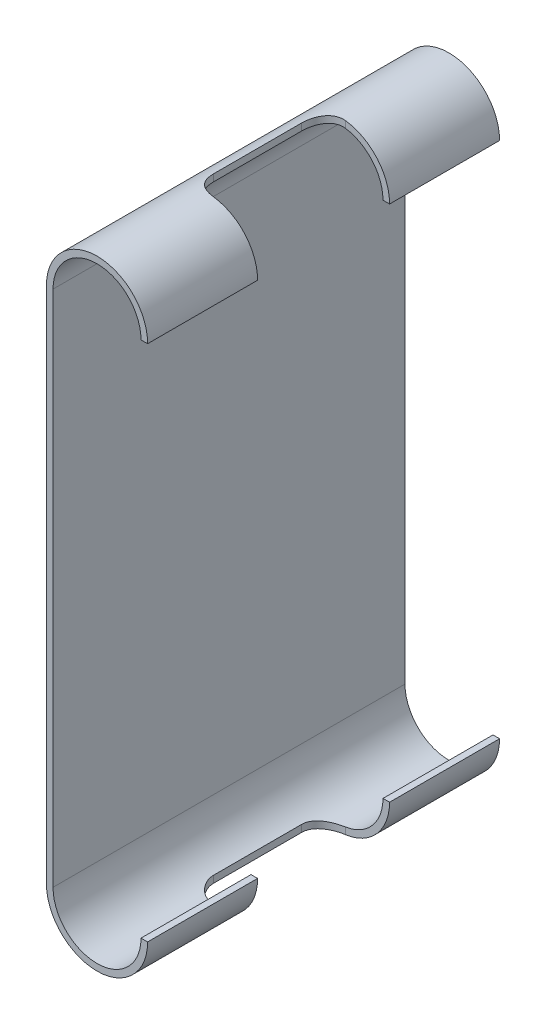
SolidWorks part; units mm, degrees
ref_plane "Front Plane" through (0, 0, 0) normal (0, 0, 1) x (1, 0, 0)
ref_plane "Top Plane" through (0, 0, 0) normal (0, 1, 0) x (1, 0, 0)
ref_plane "Right Plane" through (0, 0, 0) normal (1, 0, 0) x (0, 0, -1)
sketch "Sketch1" plane through (0, 0, 0) normal (0, 0, 1) x (1, 0, 0)
  line L0 (0, -75) -> (-40, -75) construction
  line L1 (33, 42.75) -> (-40, 42.75) construction
  line L3 (-40, -75) -> (-40, 160.5)
  line L4 (-43, -75) -> (-43, 160.5)
  line L5 (0, 160.5) -> (3, 160.5)
  line L6 (0, -75) -> (3, -75)
  arc A0 (-40, -75) -> (0, -75) centre (-20, -75) ccw
  arc A1 (-40, 160.5) -> (0, 160.5) centre (-20, 160.5) cw
  arc A2 (-43, 160.5) -> (3, 160.5) centre (-20, 160.5) cw
  arc A3 (-43, -75) -> (3, -75) centre (-20, -75) ccw
  dimension "D1" = 3
extrude "Boss-Extrude1" add sketch "Sketch1" against normal up to surface (160 mm away)
ref_plane "Plane1" through (3, 0, 0) normal (1, 0, 0) x (0, 0, -1)
sketch "Sketch2" plane through (3, 0, 0) normal (1, 0, 0) x (0, 0, -1)
  line L1 (50, -71.75) -> (110, -71.75)
  line L2 (50, -71.75) -> (50, -99.75)
  line L3 (50, -99.75) -> (110, -99.75)
  line L4 (110, -71.75) -> (110, -99.75)
  line L6 (193.5, 42.75) -> (-33.0117, 42.75) construction
  line L7 (193.5, 16.75) -> (193.5, 68.75) construction
  line L8 (110, 157.25) -> (110, 185.25)
  line L9 (50, 185.25) -> (110, 185.25)
  line L10 (50, 157.25) -> (50, 185.25)
  line L11 (50, 157.25) -> (110, 157.25)
  point P14 (0, 0)
extrude "Cut-Extrude1" cut sketch "Sketch2" against normal blind 30
fillet "Fillet1" radius 10 4 edges at (-27, -95.3219, -110) (-27, -95.3219, -50) (-27, 180.8219, -50) (-27, 180.8219, -110)
